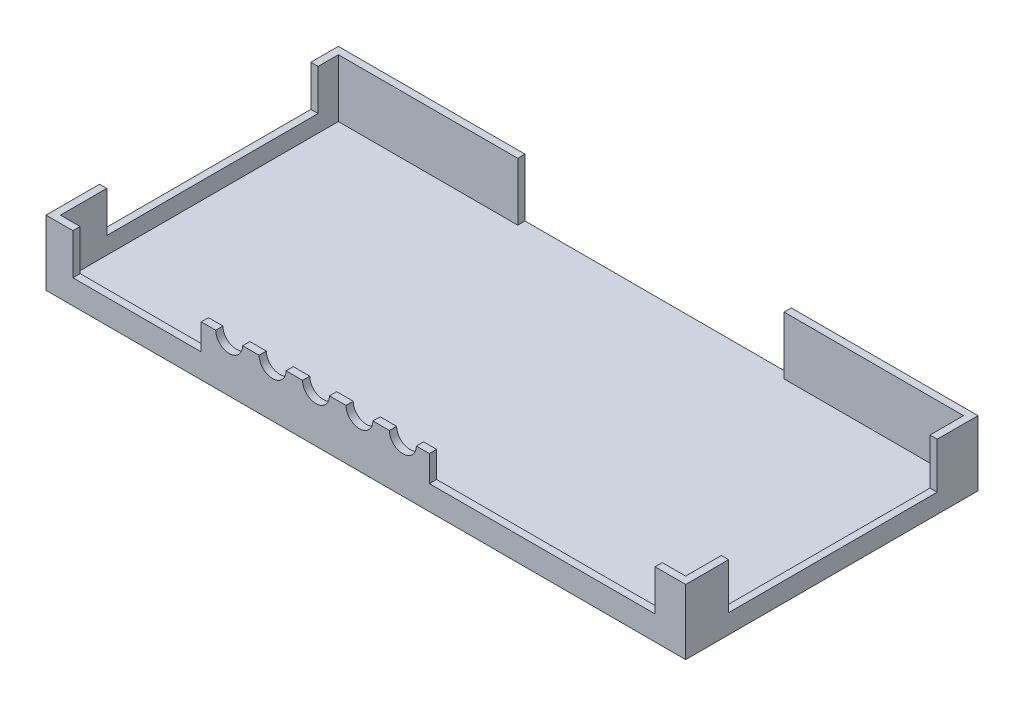
SolidWorks part; units mm, degrees
ref_plane "Front Plane" through (0, 0, 0) normal (0, 0, 1) x (1, 0, 0)
ref_plane "Top Plane" through (0, 0, 0) normal (0, 1, 0) x (1, 0, 0)
ref_plane "Right Plane" through (0, 0, 0) normal (1, 0, 0) x (0, 0, -1)
sketch "Sketch1" plane through (0, 0, 0) normal (0, 1, 0) x (1, 0, 0)
  line L0 (-110.5, -50.5) -> (-110.5, 50.5)
  line L1 (-108, -48) -> (108, -48)
  line L2 (-108, -48) -> (-108, 48)
  line L3 (-108, 48) -> (108, 48)
  line L4 (108, -48) -> (108, 48)
  line L5 (-108, -48) -> (108, 48) construction
  line L6 (-108, 48) -> (108, -48) construction
  line L7 (-110.5, 50.5) -> (110.5, 50.5)
  line L8 (110.5, -50.5) -> (110.5, 50.5)
  line L9 (-110.5, -50.5) -> (110.5, -50.5)
  point P0 (0, 0)
  dimension "D1" = 216
  dimension "D2" = 96
  dimension "D3" = 2.5
extrude "Boss-Extrude1" add sketch "Sketch1" along normal blind 20 contours L0 L9 L8 L7 L4 L1 L2 L3 region at (-108.0701, 0, 0)
extrude "Boss-Extrude2" add sketch "Sketch1<3>" against normal blind 2.5 contours L0 L7 L8 L9
sketch "Sketch1<3>" plane through (0, 0, 0) normal (0, 1, 0) x (1, 0, 0) same geometry as "Sketch1"
ref_plane "Plane1" through (-110.5, 20, 50.5) normal (1, 0, 0) x (0, 0, -1)
sketch "Sketch3" plane through (0, 0, 50.5) normal (0, 0, 1) x (1, 0, 0)
  line L0 (-110.5, 20) -> (110.5, 20) construction
  line L1 (-101.2008, 20) -> (99.9204, 20)
  line L2 (-101.2008, 20) -> (-101.2008, 5.8947)
  line L3 (-101.2008, 5.8947) -> (99.9204, 5.8947)
  line L4 (99.9204, 20) -> (99.9204, 5.8947)
extrude "Cut-Extrude1" cut sketch "Sketch3" against normal blind 10
sketch "Sketch4" plane through (110.5, 0, 0) normal (1, 0, 0) x (0, 0, -1)
  line L0 (-50.5, 20) -> (50.5, 20) construction
  line L1 (-35.6625, 20) -> (36.407, 20)
  line L2 (-35.6625, 20) -> (-35.6625, 4.1415)
  line L3 (-35.6625, 4.1415) -> (36.407, 4.1415)
  line L4 (36.407, 20) -> (36.407, 4.1415)
extrude "Cut-Extrude2" cut sketch "Sketch4" against normal blind 10
sketch "Sketch5" plane through (0, 0, 50.5) normal (0, 0, 1) x (1, 0, 0)
  line L0 (-144.165, 14.8947) -> (142.8743, 14.8947) construction
  line L1 (-101.2008, 5.8947) -> (99.9204, 5.8947) construction
  line L2 (0, -12.375) -> (0, 12.375) construction
  line L4 (-56.87, 5.8947) -> (21.95, 5.8947)
  line L6 (-42.57, 14.8947) -> (-36.87, 14.8947)
  line L7 (-27.57, 14.8947) -> (-21.87, 14.8947)
  line L8 (-12.57, 14.8947) -> (-6.86, 14.8947)
  line L9 (2.44, 14.8947) -> (8.15, 14.8947)
  line L10 (-56.87, 14.8947) -> (-56.87, 5.8947)
  line L11 (-56.87, 14.8947) -> (-51.87, 14.8947)
  line L12 (21.95, 14.8947) -> (21.95, 5.8947)
  line L13 (17.45, 14.8947) -> (21.95, 14.8947)
  circle A0 centre (-47.22, 14.8947) radius 4.65 construction
  circle A1 centre (-32.22, 14.8947) radius 4.65 construction
  circle A2 centre (-17.22, 14.8947) radius 4.65 construction
  circle A3 centre (-2.21, 14.8947) radius 4.65 construction
  circle A4 centre (12.8, 14.8947) radius 4.65 construction
  arc A5 (-51.87, 14.8947) -> (-42.57, 14.8947) centre (-47.22, 14.8947) ccw
  arc A6 (-36.87, 14.8947) -> (-27.57, 14.8947) centre (-32.22, 14.8947) ccw
  arc A7 (-21.87, 14.8947) -> (-12.57, 14.8947) centre (-17.22, 14.8947) ccw
  arc A8 (-6.86, 14.8947) -> (2.44, 14.8947) centre (-2.21, 14.8947) ccw
  arc A9 (8.15, 14.8947) -> (17.45, 14.8947) centre (12.8, 14.8947) ccw
  point P4 (-47.22, 14.8947)
  point P5 (-32.22, 14.8947)
  point P6 (-17.22, 14.8947)
  point P7 (-2.21, 14.8947)
  point P8 (12.8, 14.8947)
  dimension "D7" = 9.3
  dimension "D8" = 5
  dimension "D9" = 4.5
  dimension "D1" = 9
  dimension "D2" = 47.22
  dimension "D3" = 32.22
  dimension "D4" = 17.22
  dimension "D5" = 2.21
  dimension "D6" = 12.8
extrude "Boss-Extrude3" add sketch "Sketch5" against normal up to surface (2.5 mm away) up to face at (-0.3201, 11.4737, 48)
sketch "Sketch6" plane through (0, 0, -50.5) normal (0, 0, -1) x (-1, 0, 0)
  line L0 (110.5, 20) -> (-110.5, 20) construction
  line L1 (-46, 20) -> (46, 20)
  line L2 (-46, 20) -> (-46, 0)
  line L3 (-46, 0) -> (46, 0)
  line L4 (46, 20) -> (46, 0)
  line L5 (0, 12.375) -> (0, -12.375) construction
  dimension "D1" = 92
  dimension "D2" = 46
  dimension "D3" = 20
extrude "Cut-Extrude3" cut sketch "Sketch6" against normal blind 10
sketch "Sketch7" plane through (-110.5, 0, 0) normal (-1, 0, 0) x (0, 0, 1)
  line L0 (50.5, 20) -> (-50.5, 20) construction
  line L1 (32, 20) -> (-41, 20)
  line L2 (32, 20) -> (32, 5.9)
  line L3 (32, 5.9) -> (-41, 5.9)
  line L4 (-41, 20) -> (-41, 5.9)
  line L5 (50.5, 20) -> (50.5, -2.5) construction
  line L6 (50.5, -2.5) -> (-50.5, -2.5) construction
  dimension "D1" = 18.5
  dimension "D2" = 7
  dimension "D3" = 8.4
extrude "Cut-Extrude4" cut sketch "Sketch7" against normal blind 10
equation "\"D2@Sketch6\"=\"D1@Sketch6\"/2"
